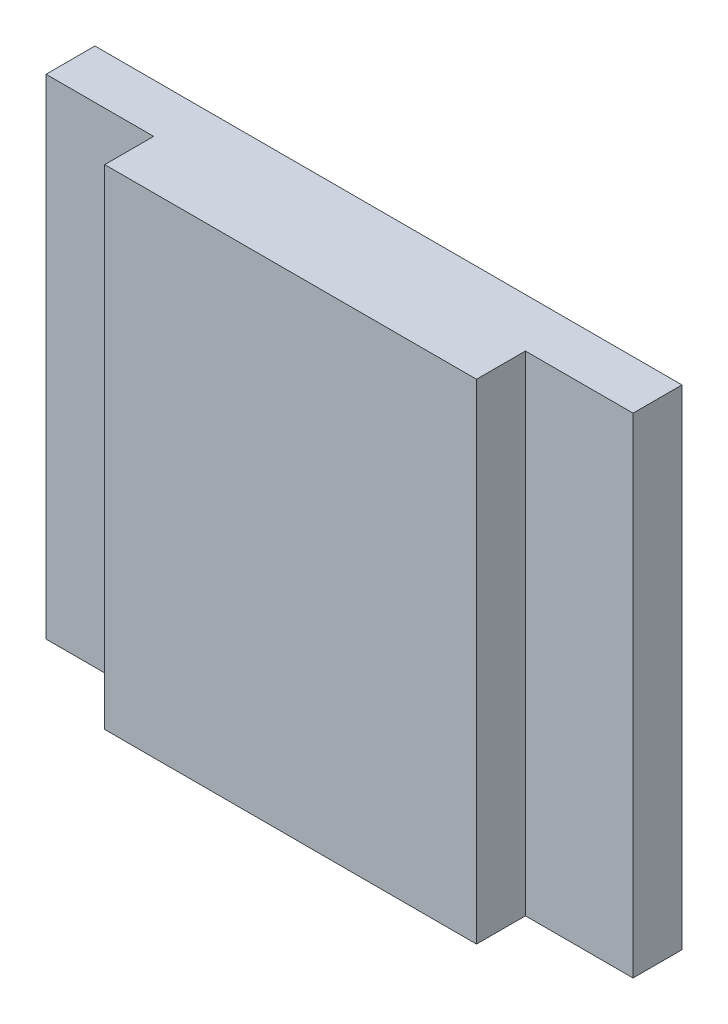
SolidWorks part; units mm, degrees
ref_plane "Front Plane" through (0, 0, 0) normal (0, 0, 1) x (1, 0, 0)
ref_plane "Top Plane" through (0, 0, 0) normal (0, 1, 0) x (1, 0, 0)
ref_plane "Right Plane" through (0, 0, 0) normal (1, 0, 0) x (0, 0, -1)
sketch "Sketch1" plane through (0, 0, 0) normal (0, 1, 0) x (1, 0, 0)
  line L0 (-25.0871, 10.5017) -> (34.9129, 10.5017)
  line L1 (34.9129, 10.5017) -> (34.9129, 5.5017)
  line L2 (34.9129, 5.5017) -> (23.9129, 5.5017)
  line L3 (23.9129, 5.5017) -> (23.9129, 0.5017)
  line L4 (23.9129, 0.5017) -> (-14.0871, 0.5017)
  line L5 (-14.0871, 0.5017) -> (-14.0871, 5.5017)
  line L6 (-14.0871, 5.5017) -> (-25.0871, 5.5017)
  line L7 (-25.0871, 5.5017) -> (-25.0871, 10.5017)
  dimension "D1" = 38
  dimension "D2" = 60
  dimension "D3" = 11
  dimension "D4" = 11
  dimension "D5" = 5
  dimension "D6" = 5
  dimension "D7" = 5
  dimension "D8" = 5
extrude "Boss-Extrude1" add sketch "Sketch1" along normal blind 50
sketch "Sketch2" plane through (0, 0, -10.5017) normal (0, 0, -1) x (-1, 0, 0)
  line L0 (-4.9129, 50) -> (-4.9129, 0) construction
  line L1 (-34.9129, 50) -> (25.0871, 50) construction
  line L2 (-34.9129, 0) -> (25.0871, 0) construction
  line L4 (-29.9129, 40) -> (20.0871, 40)
  line L5 (-29.9129, 40) -> (-29.9129, 10)
  line L6 (-29.9129, 10) -> (20.0871, 10)
  line L7 (20.0871, 40) -> (20.0871, 10)
  line L8 (-4.9129, 10) -> (-4.9129, 40) construction
  line L9 (-29.9129, 25) -> (20.0871, 25) construction
  circle A0 centre (-29.9129, 40) radius 2.5
  circle A1 centre (-29.9129, 10) radius 2.5
  circle A2 centre (20.0871, 39.5167) radius 2.5
  circle A3 centre (20.0871, 10) radius 2.5
  point P6 (-4.9129, 25)
  dimension "D1" = 30
  dimension "D2" = 50
extrude "Cut-Extrude1" cut sketch "Sketch2" against normal blind 1 contours A0 | A1 | A2 | A3
